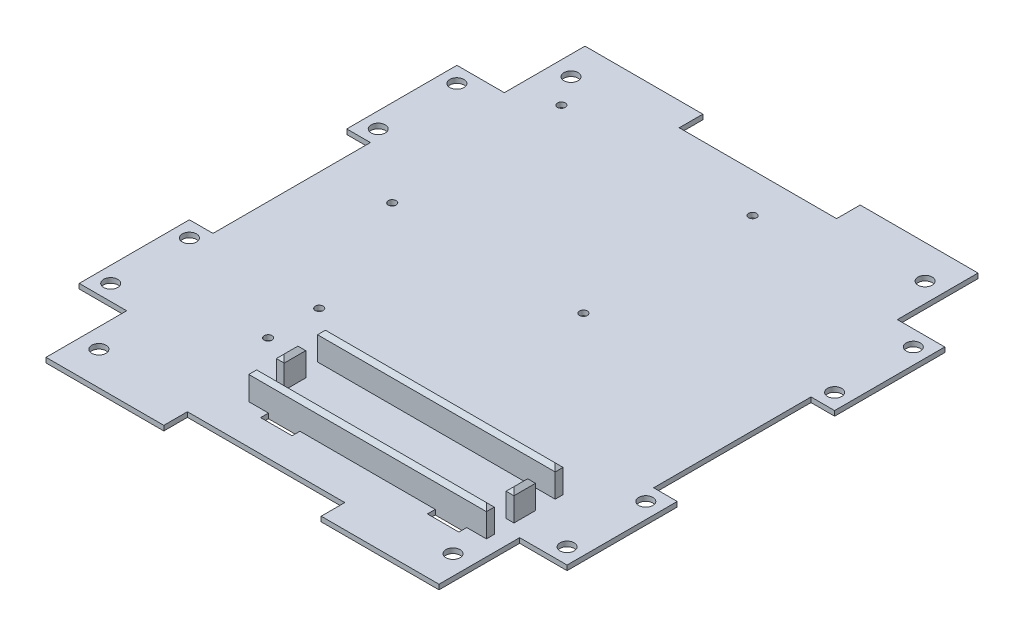
SolidWorks part; units mm, degrees
ref_plane "Front Plane" through (0, 0, 0) normal (0, 0, 1) x (1, 0, 0)
ref_plane "Top Plane" through (0, 0, 0) normal (0, 1, 0) x (1, 0, 0)
ref_plane "Right Plane" through (0, 0, 0) normal (1, 0, 0) x (0, 0, -1)
sketch "Sketch1" plane through (0, 0, 0) normal (0, 1, 0) x (1, 0, 0)
  line L0 (-25.4, 86.995) -> (-63.4314, 86.995)
  line L1 (-88.9, -101.6) -> (88.9, -101.6) construction
  line L2 (101.6, -88.9) -> (101.6, 88.9) construction
  line L3 (88.9, 101.6) -> (-88.9, 101.6) construction
  line L4 (-78.74, -60.96) -> (-63.4314, -60.96)
  line L5 (-63.4314, -60.96) -> (-63.4314, -86.995)
  line L6 (-63.4314, -86.995) -> (-25.4, -86.995)
  line L7 (63.4314, -86.995) -> (63.4314, -60.96)
  line L8 (63.4314, -60.96) -> (78.74, -60.96)
  line L9 (78.74, -60.96) -> (78.74, -25.4)
  line L10 (78.74, 60.96) -> (63.4314, 60.96)
  line L11 (63.4314, 60.96) -> (63.4314, 86.995)
  line L12 (63.4314, 86.995) -> (25.4, 86.995)
  line L13 (-63.4314, 86.995) -> (-63.4314, 60.96)
  line L14 (-63.4314, 60.96) -> (-78.74, 60.96)
  line L15 (-78.74, 60.96) -> (-78.74, 25.4)
  line L16 (-78.74, -25.4) -> (-78.74, -60.96)
  line L17 (-78.74, -25.4) -> (-71.12, -25.4)
  line L19 (-78.74, 25.4) -> (-71.12, 25.4)
  line L20 (-71.12, -25.4) -> (-71.12, 25.4)
  line L22 (-25.4, 86.995) -> (-25.4, 79.375)
  line L23 (-25.4, 79.375) -> (25.4, 79.375)
  line L24 (25.4, 86.995) -> (25.4, 79.375)
  line L25 (78.74, 25.4) -> (71.12, 25.4)
  line L27 (78.74, -25.4) -> (71.12, -25.4)
  line L28 (71.12, 25.4) -> (71.12, -25.4)
  line L30 (25.4, -86.995) -> (25.4, -79.375)
  line L31 (25.4, -79.375) -> (-25.4, -79.375)
  line L32 (-25.4, -86.995) -> (-25.4, -79.375)
  line L33 (78.74, 25.4) -> (78.74, 60.96)
  line L34 (25.4, -86.995) -> (63.4314, -86.995)
  line L35 (-101.6, 88.9) -> (-101.6, -88.9) construction
  arc A0 (88.9, -101.6) -> (101.6, -88.9) centre (88.9, -88.9) ccw construction
  arc A1 (-101.6, -88.9) -> (-88.9, -101.6) centre (-88.9, -88.9) ccw construction
  arc A2 (101.6, 88.9) -> (88.9, 101.6) centre (88.9, 88.9) ccw construction
  arc A3 (-101.6, 88.9) -> (-88.9, 101.6) centre (-88.9, 88.9) cw construction
  circle A4 centre (-57.15, 76.2) radius 2.286
  circle A5 centre (57.15, 76.2) radius 2.286
  circle A6 centre (57.15, -76.2) radius 2.286
  circle A7 centre (-57.15, -76.2) radius 2.286
  point P3 (0, 101.6)
  point P5 (101.6, 0)
  point P13 (101.6, 101.6)
  point P16 (-101.6, 101.6)
  point P38 (-71.12, 0)
  point P55 (0, -79.375)
  point P56 (0, 79.375)
  point P57 (71.12, 0)
  dimension "D2" = 12.7
  dimension "D11" = 4.572
  dimension "D8" = 44.45
  dimension "D1" = 203.2
  dimension "D3" = 203.2
  dimension "D4" = 22.86
  dimension "D5" = 15.3086
  dimension "D6" = 35.56
  dimension "D7" = 173.99
  dimension "D12" = 50.8
  dimension "D13" = 25.4
  dimension "D14" = 44.45
  dimension "D15" = 25.4
  dimension "D18" = 7.62
extrude "Boss-Extrude1" add sketch "Sketch1" along normal blind 1.5875
sketch "Sketch2" plane through (0, 1.5875, 0) normal (0, 1, 0) x (1, 0, 0)
  line L0 (0, -1000) -> (0, 49000) construction
  line L1 (-1000, 0) -> (49000, 0) construction
  line L2 (-78.74, -60.96) -> (-63.4314, -60.96) construction
  line L3 (-71.12, -25.4) -> (-78.74, -25.4) construction
  line L4 (-78.74, -25.4) -> (-78.74, -60.96) construction
  circle A0 centre (-73.66, -30.48) radius 2.286
  circle A1 centre (-73.66, -55.88) radius 2.286
  circle A2 centre (73.66, -55.88) radius 2.286
  circle A3 centre (73.66, -30.48) radius 2.286
  circle A4 centre (73.66, 30.48) radius 2.286
  circle A5 centre (73.66, 55.88) radius 2.286
  circle A6 centre (-73.66, 55.88) radius 2.286
  circle A7 centre (-73.66, 30.48) radius 2.286
  dimension "D1" = 4.572
  dimension "D2" = 5.08
  dimension "D3" = 5.08
  dimension "D4" = 5.08
extrude "Cut-Extrude1" cut sketch "Sketch2" against normal through all
sketch "Sketch3" plane through (0, 1.5875, 0) normal (0, 1, 0) x (1, 0, 0)
  line L0 (-63.4314, 86.995) -> (-63.4314, 60.96) construction
  line L1 (-50.7314, 66.675) -> (10.9906, 66.675) construction
  line L2 (-50.7314, 66.675) -> (-50.7314, 12.065) construction
  line L3 (-50.7314, 12.065) -> (10.9906, 12.065) construction
  line L4 (10.9906, 66.675) -> (10.9906, 12.065) construction
  line L5 (25.4, 79.375) -> (-25.4, 79.375) construction
  circle A0 centre (-50.7314, 66.675) radius 1.27
  circle A1 centre (10.9906, 66.675) radius 1.27
  circle A2 centre (10.9906, 12.065) radius 1.27
  circle A3 centre (-50.7314, 12.065) radius 1.27
  dimension "D3" = 2.54
  dimension "D1" = 54.61
  dimension "D2" = 61.722
  dimension "D4" = 12.7
  dimension "D5" = 12.7
extrude "Cut-Extrude2" cut sketch "Sketch3" against normal through all
sketch "Sketch4" plane through (0, 1.5875, 0) normal (0, 1, 0) x (1, 0, 0)
  line L20 (-15.748, -44.4754) -> (55.88, -44.4754)
  line L21 (-15.748, -50.8254) -> (-15.748, -57.785)
  line L22 (-15.748, -64.135) -> (55.88, -64.135)
  line L23 (-18.288, -41.9354) -> (58.42, -41.9354)
  line L24 (58.42, -41.9354) -> (58.42, -44.4754)
  line L25 (-18.288, -66.675) -> (58.42, -66.675)
  line L26 (-18.288, -41.9354) -> (-18.288, -44.4754)
  line L27 (-15.748, -44.4754) -> (-18.288, -44.4754)
  line L28 (-15.748, -50.8254) -> (-18.288, -50.8254)
  line L29 (-18.288, -50.8254) -> (-18.288, -57.785)
  line L30 (-15.748, -57.785) -> (-18.288, -57.785)
  line L31 (55.88, -64.135) -> (58.42, -64.135)
  line L32 (55.88, -44.4754) -> (58.42, -44.4754)
  line L33 (58.42, -64.135) -> (58.42, -66.675)
  line L34 (-18.288, -64.135) -> (-18.288, -66.675)
  line L35 (-15.748, -64.135) -> (-18.288, -64.135)
  line L36 (58.42, -50.8254) -> (55.88, -50.8254)
  line L37 (58.42, -50.8254) -> (58.42, -57.785)
  line L38 (58.42, -57.785) -> (55.88, -57.785)
  line L39 (55.88, -50.8254) -> (55.88, -57.785)
  line L40 (71.12, -25.4) -> (71.12, 25.4) construction
  line L41 (-25.4, -79.375) -> (25.4, -79.375) construction
  point P17 (-17.018, -57.785)
  point P25 (0, 0)
  point P26 (0, 0)
  point P27 (-17.9786, -66.675)
  point P28 (-54.9106, -41.9354)
  point P29 (0, 0)
  point P30 (41.4098, -64.135)
  point P31 (0, 0)
  point P32 (0, 0)
  point P33 (-15.748, -64.135)
  dimension "D1" = 19.6596
  dimension "D2" = 71.628
  dimension "D3" = 6.35
  dimension "D4" = 6.35
  dimension "D5" = 6.35
  dimension "D6" = 6.35
  dimension "D7" = 2.54
  dimension "D8" = 2.54
  dimension "D9" = 12.7
  dimension "D10" = 12.7
  dimension "D11" = 6.9596
  dimension "D12" = 2.54
  dimension "D13" = 6.9596
  dimension "D14" = 2.54
extrude "Boss-Extrude2" add sketch "Sketch4" along normal blind 8.89
chamfer "Chamfer1" distance 1.27 angle 45 16 edges at (57.15, 10.4775, 57.785) (55.88, 10.4775, 54.3052) (57.15, 10.4775, 50.8254) (58.42, 10.4775, 54.3052) (58.42, 10.4775, 65.405) (20.066, 10.4775, 66.675) (-18.288, 10.4775, 65.405) (20.066, 10.4775, 64.135) (-15.748, 10.4775, 54.3052) (-17.018, 10.4775, 57.785) (-18.288, 10.4775, 54.3052) (-17.018, 10.4775, 50.8254) (-18.288, 10.4775, 43.2054) (20.066, 10.4775, 41.9354) (58.42, 10.4775, 43.2054) (20.066, 10.4775, 44.4754)
sketch "Sketch5" plane through (0, 1.5875, 0) normal (0, 1, 0) x (1, 0, 0)
  line L0 (58.42, -41.9354) -> (-18.288, -41.9354) construction
  line L1 (-11.938, -41.9354) -> (-1.778, -41.9354)
  line L2 (-11.938, -41.9354) -> (-11.938, -39.3954)
  line L3 (-11.938, -39.3954) -> (-1.778, -39.3954)
  line L4 (-1.778, -41.9354) -> (-1.778, -39.3954)
  line L5 (-18.288, -41.9354) -> (58.42, -41.9354) construction
  line L6 (52.07, -41.9354) -> (41.91, -41.9354)
  line L7 (52.07, -41.9354) -> (52.07, -39.3954)
  line L8 (52.07, -39.3954) -> (41.91, -39.3954)
  line L9 (41.91, -41.9354) -> (41.91, -39.3954)
  line L10 (-18.288, -66.675) -> (58.42, -66.675) construction
  line L11 (52.07, -66.675) -> (41.91, -66.675)
  line L12 (52.07, -66.675) -> (52.07, -69.215)
  line L13 (52.07, -69.215) -> (41.91, -69.215)
  line L14 (41.91, -66.675) -> (41.91, -69.215)
  line L15 (-18.288, -64.135) -> (-18.288, -66.675) construction
  line L16 (-1.778, -66.675) -> (-11.938, -66.675)
  line L17 (-1.778, -66.675) -> (-1.778, -69.215)
  line L18 (-1.778, -69.215) -> (-11.938, -69.215)
  line L19 (-11.938, -66.675) -> (-11.938, -69.215)
  line L20 (-18.288, -44.4754) -> (-18.288, -41.9354) construction
  line L21 (58.42, -66.675) -> (58.42, -64.135) construction
  line L22 (58.42, -41.9354) -> (58.42, -44.4754) construction
  dimension "D1" = 2.54
  dimension "D2" = 6.35
  dimension "D3" = 6.35
  dimension "D4" = 6.35
  dimension "D5" = 6.35
  dimension "D6" = 10.16
extrude "Cut-Extrude3" cut sketch "Sketch5" against normal through all
sketch "Sketch6" plane through (0, 1.5875, 0) normal (0, 1, 0) x (1, 0, 0)
  line L0 (-33.02, -29.21) -> (-33.02, -45.72) construction
  line L1 (-30.48, -26.67) -> (-58.42, -26.67) construction
  line L2 (-30.48, -26.67) -> (-30.48, -48.26) construction
  line L3 (-30.48, -48.26) -> (-58.42, -48.26) construction
  line L4 (-58.42, -26.67) -> (-58.42, -48.26) construction
  line L5 (-78.74, -60.96) -> (-63.4314, -60.96) construction
  line L6 (-71.12, 25.4) -> (-71.12, -25.4) construction
  circle A2 centre (-33.02, -29.21) radius 1.27
  circle A3 centre (-33.02, -45.72) radius 1.27
  point P8 (-33.02, -37.465)
  point P9 (-30.48, -37.465)
  dimension "D5" = 2.54
  dimension "D3" = 2.54
  dimension "D4" = 16.51
  dimension "D1" = 21.59
  dimension "D2" = 27.94
  dimension "D6" = 12.7
  dimension "D7" = 12.7
extrude "Cut-Extrude4" cut sketch "Sketch6" against normal blind 8.89
